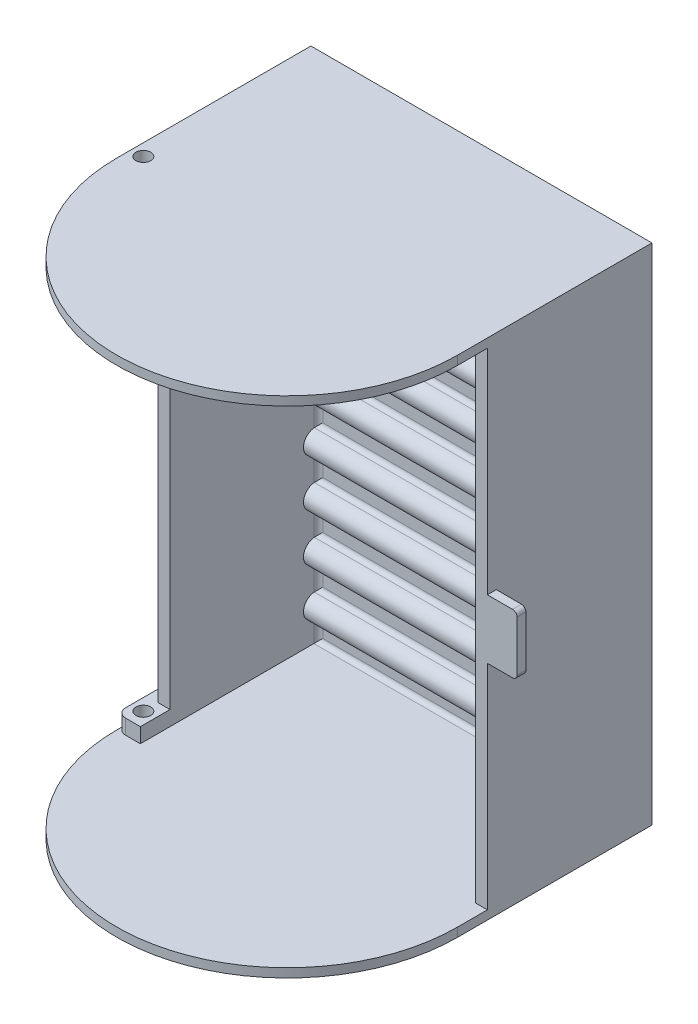
SolidWorks part; units mm, degrees
ref_plane "前基準面" through (0, 0, 0) normal (0, 0, 1) x (1, 0, 0)
ref_plane "上基準面" through (0, 0, 0) normal (0, 1, 0) x (1, 0, 0)
ref_plane "右基準面" through (0, 0, 0) normal (1, 0, 0) x (0, 0, -1)
sketch "草圖2" plane through (0, 0, 0) normal (0, 0, 1) x (1, 0, 0)
  line L1 (-58.75, 90) -> (56.25, 90)
  line L2 (-58.75, 90) -> (-58.75, -80)
  line L3 (-58.75, -80) -> (56.25, -80)
  line L4 (56.25, 90) -> (56.25, -80)
  line L5 (-58.75, 90) -> (56.25, -80) construction
  line L6 (-58.75, -80) -> (56.25, 90) construction
  point P0 (0, 0)
  dimension "D1" = 115
  dimension "D2" = 170
extrude "填料-伸長2" add sketch "草圖2" along normal blind 2.5
sketch "草圖4" plane through (0, -80, 0) normal (0, -1, 0) x (1, 0, 0)
  line L0 (-58.75, 2.5) -> (-58.75, 62.5)
  line L14 (56.25, 62.5) -> (56.25, 2.5)
  line L15 (56.25, 2.5) -> (-58.75, 2.5)
  line L16 (56.25, 2.5) -> (56.25, 0) construction
  arc A1 (-58.75, 62.5) -> (56.25, 62.5) centre (-1.25, 62.5) cw
  dimension "D2" = 60
extrude "填料-伸長5" add sketch "草圖4" against normal blind 3
sketch "草圖5" plane through (0, 90, 0) normal (0, 1, 0) x (1, 0, 0)
  line L0 (-58.75, -2.5) -> (-58.75, -62.5)
  line L2 (56.25, -62.5) -> (56.25, -2.5)
  line L3 (56.25, -2.5) -> (-58.75, -2.5)
  arc A0 (-58.75, -62.5) -> (56.25, -62.5) centre (-1.25, -62.5) ccw
extrude "填料-伸長6" add sketch "草圖5" against normal blind 3
sketch "草圖7" plane through (-58.75, 0, 0) normal (-1, 0, 0) x (0, 0, 1)
  line L0 (2.5, 87) -> (62.5, 87)
  line L1 (62.5, 87) -> (62.5, 82)
  line L2 (62.5, 82) -> (52.5, 82)
  line L4 (52.5, 82) -> (52.5, -72)
  line L6 (52.5, -72) -> (62.5, -72)
  line L7 (62.5, -72) -> (62.5, -77)
  line L8 (62.5, -77) -> (2.5, -77)
  line L9 (2.5, -77) -> (2.5, 87)
  dimension "D1" = 10
  dimension "D2" = 5
extrude "填料-伸長8" add sketch "草圖7" against normal blind 8
sketch "草圖8" plane through (0, 82, 0) normal (0, -1, 0) x (1, 0, 0)
  line L0 (-58.75, 52.5) -> (-58.75, 62.5) construction
  line L1 (-50.75, 62.5) -> (-58.75, 62.5) construction
  circle A0 centre (-54.75, 57.5) radius 2.5
  dimension "D1" = 5
  dimension "D2" = 4
  dimension "D3" = 5
extrude "除料-伸長1" cut sketch "草圖8" against normal blind 20 and the other way blind 188
fillet "圓角1" radius 3 2 edges at (-58.75, -74.5, 62.5) (-58.75, 84.5, 62.5)
sketch "草圖10" plane through (0, 0, 2.5) normal (0, 0, 1) x (1, 0, 0)
  line L0 (52.25, 87) -> (56.25, 87)
  line L1 (56.25, 87) -> (56.25, -77)
  line L2 (56.25, -77) -> (52.25, -77)
  line L3 (52.25, -77) -> (52.25, 87)
  dimension "D1" = 4
extrude "填料-伸長9" add sketch "草圖10" along normal up to surface (50 mm away) up to face at (-54.75, 5, 52.5)
sketch "草圖12" plane through (56.25, 0, 0) normal (1, 0, 0) x (0, 0, -1)
  line L1 (-52.5, 15) -> (-49.5, 15)
  line L2 (-52.5, 15) -> (-52.5, -5)
  line L3 (-52.5, -5) -> (-49.5, -5)
  line L4 (-49.5, 15) -> (-49.5, -5)
  line L5 (-52.5, 15) -> (-49.5, -5) construction
  line L6 (-52.5, -5) -> (-49.5, 15) construction
  line L11 (-52.5, -77) -> (-52.5, 87) construction
  dimension "D1" = 20
  dimension "D2" = 3
extrude "填料-伸長10" add sketch "草圖12" along normal blind 10
sketch "草圖14" plane through (-50.75, 0, 0) normal (1, 0, 0) x (0, 0, -1)
  line L13 (-2.5, -54) -> (-3.5, -54)
  line L14 (-3.5, -46) -> (-2.5, -46)
  line L15 (-2.5, -70) -> (-3.5, -70)
  line L16 (-2.5, 87) -> (-2.5, -77) construction
  line L17 (-3.5, -62) -> (-2.5, -62)
  line L18 (-2.5, -62) -> (-2.5, -70)
  line L19 (-2.5, -77) -> (-62.5, -77) construction
  line L20 (-2.5, -46) -> (-2.5, -54)
  line L21 (-2.5, -38) -> (-3.5, -38)
  line L22 (-3.5, -30) -> (-2.5, -30)
  line L23 (-2.5, -30) -> (-2.5, -38)
  line L24 (-2.5, -22) -> (-3.5, -22)
  line L25 (-3.5, -14) -> (-2.5, -14)
  line L26 (-2.5, -14) -> (-2.5, -22)
  line L27 (-2.5, -6) -> (-3.5, -6)
  line L28 (-3.5, 2) -> (-2.5, 2)
  line L29 (-2.5, 2) -> (-2.5, -6)
  line L30 (-2.5, 10) -> (-3.5, 10)
  line L31 (-3.5, 18) -> (-2.5, 18)
  line L32 (-2.5, 18) -> (-2.5, 10)
  line L33 (-2.5, 26) -> (-3.5, 26)
  line L34 (-3.5, 34) -> (-2.5, 34)
  line L35 (-2.5, 34) -> (-2.5, 26)
  line L36 (-2.5, 42) -> (-3.5, 42)
  line L37 (-3.5, 50) -> (-2.5, 50)
  line L38 (-2.5, 50) -> (-2.5, 42)
  line L39 (-2.5, 58) -> (-3.5, 58)
  line L40 (-3.5, 66) -> (-2.5, 66)
  line L41 (-2.5, 66) -> (-2.5, 58)
  line L42 (-2.5, 74) -> (-3.5, 74)
  line L43 (-3.5, 82) -> (-2.5, 82)
  line L44 (-2.5, 82) -> (-2.5, 74)
  arc A12 (-3.5, -70) -> (-3.5, -62) centre (-3.5, -66) cw
  arc A13 (-3.5, -54) -> (-3.5, -46) centre (-3.5, -50) cw
  arc A14 (-3.5, -38) -> (-3.5, -30) centre (-3.5, -34) cw
  arc A15 (-3.5, -22) -> (-3.5, -14) centre (-3.5, -18) cw
  arc A16 (-3.5, -6) -> (-3.5, 2) centre (-3.5, -2) cw
  arc A17 (-3.5, 10) -> (-3.5, 18) centre (-3.5, 14) cw
  arc A18 (-3.5, 26) -> (-3.5, 34) centre (-3.5, 30) cw
  arc A19 (-3.5, 42) -> (-3.5, 50) centre (-3.5, 46) cw
  arc A20 (-3.5, 58) -> (-3.5, 66) centre (-3.5, 62) cw
  arc A21 (-3.5, 74) -> (-3.5, 82) centre (-3.5, 78) cw
  dimension "D1" = 1
  dimension "D2" = 4
  dimension "D3" = 7
  dimension "D4" = 10
extrude "填料-伸長11" add sketch "草圖14" along normal up to next
fillet "圓角3" radius 1.5 42 edges at (0.75, -77, 2.5) (52.25, -73.5, 2.5) (-50.75, -73.5, 2.5) (66.25, 15, 51) (66.25, -5, 51) (0.75, -62, 2.5) (0.75, -70, 2.5) (0.75, 66, 2.5) (-50.75, 70, 2.5) (0.75, 74, 2.5) (52.25, 70, 2.5) (0.75, 50, 2.5) (-50.75, 54, 2.5) (0.75, 58, 2.5) (52.25, 54, 2.5) (0.75, 34, 2.5) (-50.75, 38, 2.5) (0.75, 42, 2.5) (52.25, 38, 2.5) (0.75, 18, 2.5) (-50.75, 22, 2.5) (0.75, 26, 2.5) (52.25, 22, 2.5) (0.75, 2, 2.5) (-50.75, 6, 2.5) (0.75, 10, 2.5) (52.25, 6, 2.5) (0.75, -14, 2.5) (-50.75, -10, 2.5) (0.75, -6, 2.5) (52.25, -10, 2.5) (0.75, -30, 2.5) (-50.75, -26, 2.5) (0.75, -22, 2.5) (52.25, -26, 2.5) (0.75, -46, 2.5) (-50.75, -42, 2.5) (0.75, -38, 2.5) (52.25, -42, 2.5) (-50.75, -58, 2.5) (0.75, -54, 2.5) (52.25, -58, 2.5)
sketch "草圖15" plane through (0, 0, 0) normal (0, 0, -1) x (-1, 0, 0)
  line L0 (58.75, 90) -> (58.75, -80) construction
  line L1 (-56.25, 90) -> (58.75, 90)
  line L2 (-56.25, 90) -> (-56.25, -80)
  line L3 (-56.25, -80) -> (58.75, -80)
  line L4 (58.75, 90) -> (58.75, -80)
  line L5 (58.75, -80) -> (-56.25, -80) construction
  point P7 (58.75, 82)
  point P8 (58.75, -80)
extrude "填料-伸長12" add sketch "草圖15" along normal blind 3
sketch "草圖16" plane through (0, 0, 52.5) normal (0, 0, 1) x (1, 0, 0)
  line L1 (-58.75, 82) -> (-54.75, 82)
  line L2 (-58.75, 82) -> (-58.75, -72)
  line L3 (-58.75, -72) -> (-54.75, -72)
  line L4 (-54.75, 82) -> (-54.75, -72)
  dimension "D1" = 4
extrude "除料-伸長2" cut sketch "草圖16" against normal through all
sketch "草圖17" plane through (0, 0, -3) normal (0, 0, -1) x (-1, 0, 0)
  line L0 (1.25, 12.5) -> (1.25, -2.5) construction
  line L3 (-56.25, 90) -> (58.75, -80) construction
  line L4 (58.75, 90) -> (-56.25, -80) construction
  line L5 (-56.25, -80) -> (58.75, -80) construction
  line L6 (-56.25, 90) -> (-56.25, -80) construction
  line L7 (8.75, 12.5) -> (8.75, -2.5)
  line L8 (-6.25, 12.5) -> (-6.25, -2.5)
  arc A2 (8.75, 12.5) -> (-6.25, 12.5) centre (1.25, 12.5) ccw
  arc A3 (-6.25, -2.5) -> (8.75, -2.5) centre (1.25, -2.5) ccw
  point P2 (1.25, 5)
  dimension "D2" = 7.5
  dimension "D1" = 30
extrude "除料-伸長3" cut sketch "草圖17" against normal blind 3.4
